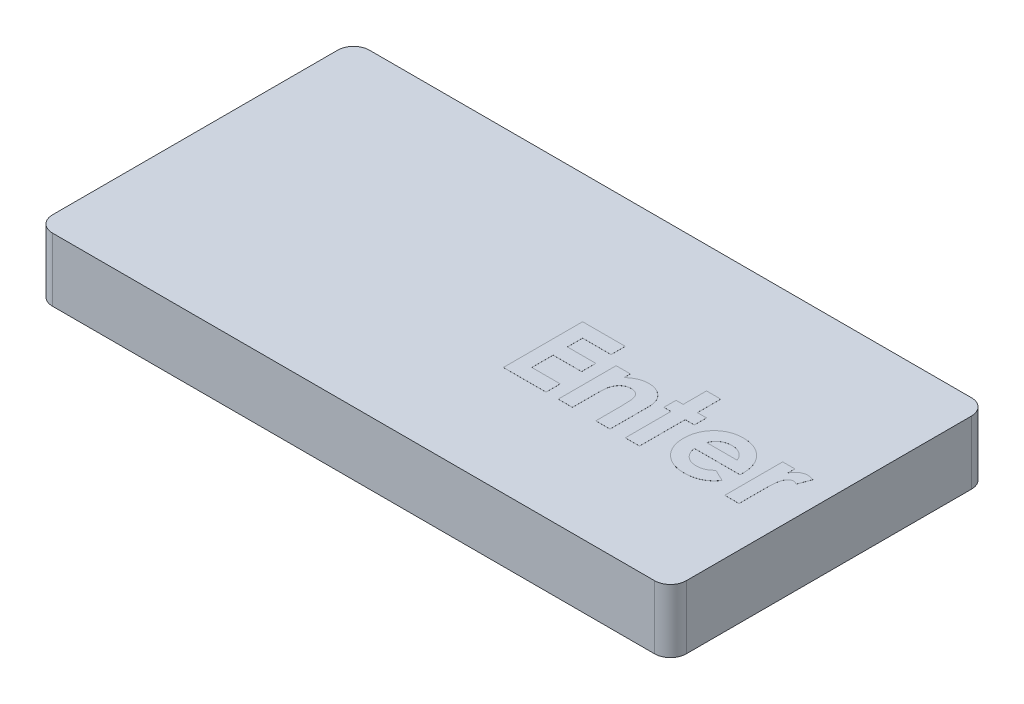
SolidWorks part; units mm, degrees
ref_plane "Front Plane" through (0, 0, 0) normal (0, 0, 1) x (1, 0, 0)
ref_plane "Top Plane" through (0, 0, 0) normal (0, 1, 0) x (1, 0, 0)
ref_plane "Right Plane" through (0, 0, 0) normal (1, 0, 0) x (0, 0, -1)
sketch "Sketch1" plane through (0, 0, 0) normal (0, 1, 0) x (1, 0, 0)
  line L0 (0, 0) -> (25.4, 0)
  line L1 (25.4, 0) -> (25.4, 12.7)
  line L2 (25.4, 12.7) -> (0, 12.7)
  line L3 (0, 12.7) -> (0, 0)
  dimension "D1" = 25.4
  dimension "D2" = 12.7
extrude "Boss-Extrude1" add sketch "Sketch1" along normal blind 2.54
fillet "Fillet1" radius 0.635 4 edges at (0, 1.27, -12.7) (25.4, 1.27, -12.7) (25.4, 1.27, 0) (0, 1.27, 0)
shell "Shell1" thickness 0.635 removed face at (12.7, 0, -6.35)
sketch "Sketch2" plane through (0, 1.905, 0) normal (0, -1, 0) x (-1, 0, 0)
  line L0 (-0.635, 6.35) -> (-24.765, 6.35) construction
  line L1 (-0.635, 12.065) -> (-0.635, 0.635) construction
  line L2 (-24.765, 0.635) -> (-24.765, 12.065) construction
  line L3 (-12.7, 0.635) -> (-12.7, 12.065) construction
  line L4 (-0.635, 0.635) -> (-24.765, 0.635) construction
  line L5 (-24.765, 12.065) -> (-0.635, 12.065) construction
  circle A0 centre (-12.7, 6.35) radius 2.54
  dimension "D1" = 5.08
extrude "Boss-Extrude2" add sketch "Sketch2" along normal up to surface (1.905 mm away) up to face at (12.7, 0, -6.35)
sketch "Sketch3" plane through (0, 2.54, 0) normal (0, 1, 0) x (1, 0, 0)
  line L0 (0.635, 0) -> (24.765, 0) construction
  line L1 (0, 12.065) -> (0, 0.635) construction
  text T0 "<b>Enter</b>"
  dimension "D1" = 4.3688
  dimension "D2" = 13.97
extrude "Boss-Extrude3" add sketch "Sketch3" along normal blind 0.0025
